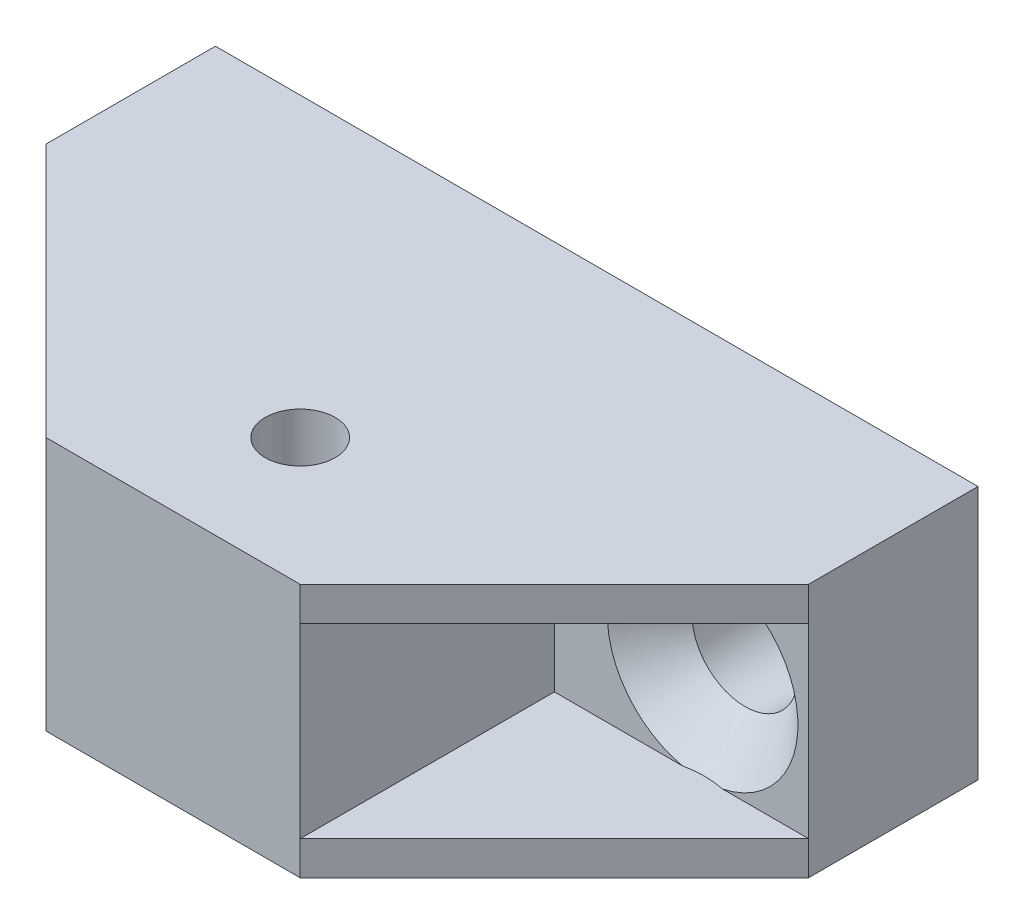
SolidWorks part; units mm, degrees
ref_plane "Plan de face" through (0, 0, 0) normal (0, 0, 1) x (1, 0, 0)
ref_plane "Plan de dessus" through (0, 0, 0) normal (0, 1, 0) x (1, 0, 0)
ref_plane "Plan de droite" through (0, 0, 0) normal (1, 0, 0) x (0, 0, -1)
sketch "Esquisse1" plane through (0, 0, 0) normal (0, 0, 1) x (1, 0, 0)
  line L1 (0, 0) -> (36, 0)
  line L2 (0, 0) -> (0, 12)
  line L3 (0, 12) -> (36, 12)
  line L4 (36, 0) -> (36, 12)
  dimension "D1" = 12
  dimension "D2" = 36
extrude "Boss.-Extru.1" add sketch "Esquisse1" along normal blind 8
sketch "Esquisse2" plane through (0, 0, 8) normal (0, 0, 1) x (1, 0, 0)
  line L0 (0, 6) -> (18, 6) construction
  line L1 (0, 12) -> (0, 0) construction
  line L2 (18, 6) -> (18, 12) construction
  line L3 (36, 12) -> (0, 12) construction
  circle A0 centre (5, 6) radius 2.5
  circle A1 centre (31, 6) radius 2.5
  dimension "D1" = 26
  dimension "D2" = 5
extrude "Enlèv. mat.-Extru.1" cut sketch "Esquisse2" against normal through all both and the other way through all
sketch "Esquisse3" plane through (0, 12, 0) normal (0, 1, 0) x (1, 0, 0)
  line L0 (36, -8) -> (0, -8) construction
  line L1 (12, -8) -> (24, -8)
  line L2 (12, -8) -> (12, -20)
  line L3 (12, -20) -> (24, -20)
  line L4 (24, -8) -> (24, -20)
  line L5 (18, -20) -> (18, 0) construction
  line L6 (36, 0) -> (0, 0) construction
  dimension "D1" = 12
  dimension "D2" = 12
extrude "Boss.-Extru.2" add sketch "Esquisse3" against normal up to vertex (12 mm away) up to point (0, 0, 8)
sketch "Esquisse4" plane through (0, 12, 0) normal (0, 1, 0) x (1, 0, 0)
  line L0 (18, -20) -> (18, -14) construction
  line L1 (12, -20) -> (24, -20) construction
  circle A0 centre (18, -14) radius 1.65
  dimension "D1" = 3.3
  dimension "D2" = 6
extrude "Enlèv. mat.-Extru.2" cut sketch "Esquisse4" against normal through all both and the other way through all
sketch "Esquisse5" plane through (0, 0, 0) normal (0, -1, 0) x (1, 0, 0)
  line L0 (12, 8) -> (0, 8)
  line L1 (0, 8) -> (12, 20)
  line L2 (12, 20) -> (12, 8)
  line L3 (18, 0) -> (18, 20) construction
  line L4 (0, 0) -> (36, 0) construction
  line L5 (12, 20) -> (24, 20) construction
  line L6 (24, 20) -> (24, 8)
  line L7 (36, 8) -> (24, 20)
  line L8 (24, 8) -> (36, 8)
extrude "Boss.-Extru.3" add sketch "Esquisse5" against normal blind 1.6
extrude "Boss.-Extru.4" add sketch "Esquisse5<2>" along normal blind 1.6 from vertex starting at point (12, 12, 20)
sketch "Esquisse5<2>" plane through (0, 0, 0) normal (0, -1, 0) x (1, 0, 0) same geometry as "Esquisse5"
chamfer "Chanfrein1" distance 2 angle 45 2 edges at (28.5, 6, 8) (2.5, 6, 8)
